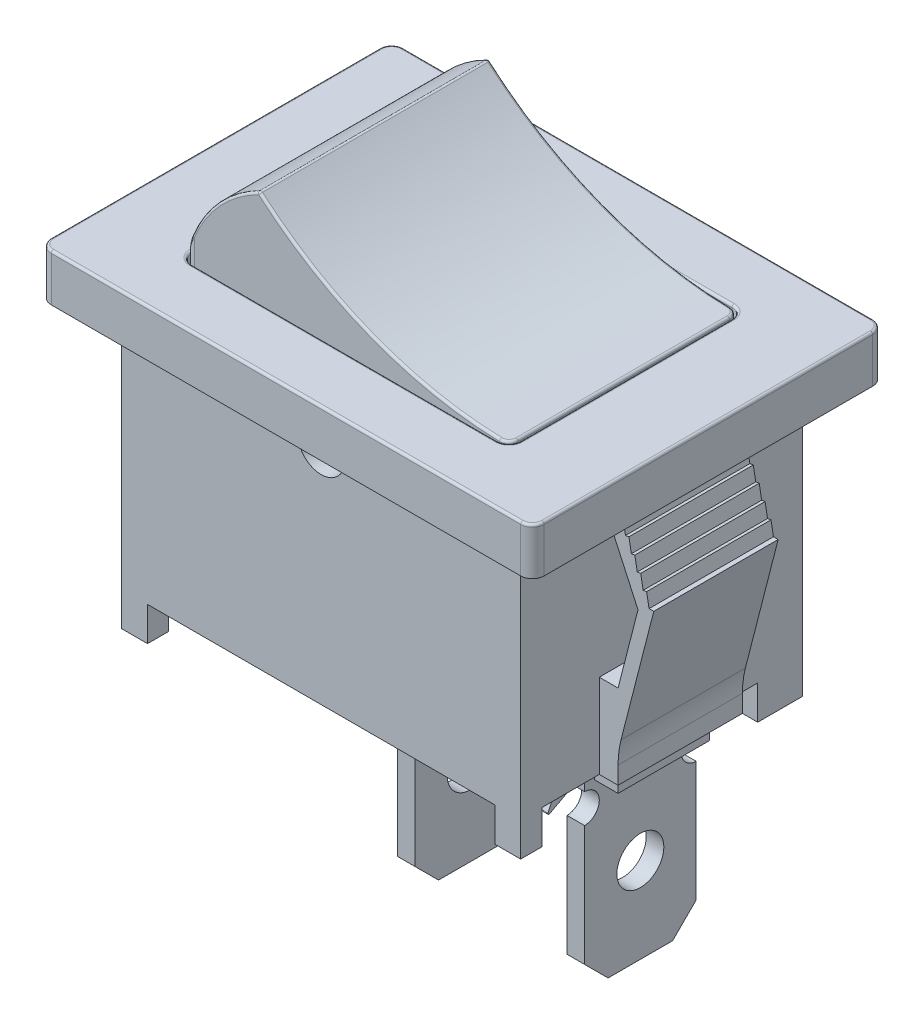
SolidWorks part; units mm, degrees
ref_plane "Front Plane" through (0, 0, 0) normal (0, 0, 1) x (1, 0, 0)
ref_plane "Top Plane" through (0, 0, 0) normal (0, 1, 0) x (1, 0, 0)
ref_plane "Right Plane" through (0, 0, 0) normal (1, 0, 0) x (0, 0, -1)
sketch "Sketch1" plane through (0, 0, 0) normal (0, 1, 0) x (1, 0, 0)
  line L0 (-8.5, 6) -> (8.5, -6) construction
  line L1 (-8.5, 6) -> (8.5, 6)
  line L2 (-8.5, 6) -> (-8.5, -6)
  line L3 (-8.5, -6) -> (8.5, -6)
  line L4 (8.5, 6) -> (8.5, -6)
  point P4 (0, 0)
  dimension "D1" = 17
  dimension "D2" = 12
extrude "Boss-Extrude1" add sketch "Sketch1" along normal blind 10.5
sketch "Sketch2" plane through (0, 10.5, 0) normal (0, 1, 0) x (1, 0, 0)
  line L0 (-10.5, 7.5) -> (10.5, -7.5) construction
  line L1 (-10.5, 7.5) -> (10.5, 7.5)
  line L2 (-10.5, 7.5) -> (-10.5, -7.5)
  line L3 (-10.5, -7.5) -> (10.5, -7.5)
  line L4 (10.5, 7.5) -> (10.5, -7.5)
  line L5 (7, 5) -> (-7, -5) construction
  line L6 (-6.5, 5) -> (6.5, 5)
  line L7 (-7, 4.5) -> (-7, -4.5)
  line L8 (-6.5, -5) -> (6.5, -5)
  line L9 (7, 4.5) -> (7, -4.5)
  arc A0 (6.5, 5) -> (7, 4.5) centre (6.5, 4.5) cw
  arc A1 (6.5, -5) -> (7, -4.5) centre (6.5, -4.5) ccw
  arc A2 (-7, -4.5) -> (-6.5, -5) centre (-6.5, -4.5) ccw
  arc A3 (-6.5, 5) -> (-7, 4.5) centre (-6.5, 4.5) ccw
  point P4 (0, 0)
  point P15 (7, -5)
  point P21 (-7, 5)
  dimension "D4" = 0.5
  dimension "D1" = 15
  dimension "D2" = 21
  dimension "D3" = 10
extrude "Boss-Extrude2" add sketch "Sketch2" along normal blind 2
sketch "Sketch3" plane through (0, 10.5, 0) normal (0, 1, 0) x (1, 0, 0)
  line L0 (7, -4.5) -> (7, 4.5) construction
  line L1 (-6.5, 5) -> (6.5, 5) construction
  line L2 (-7, 4.5) -> (-7, -4.5) construction
  line L3 (-6.5, -5) -> (6.5, -5) construction
  line L4 (7, 4.5) -> (7, -4.5) construction
  line L5 (-7, 4.5) -> (-7, -4.5) construction
  line L6 (-6.5, -5) -> (6.5, -5) construction
  line L7 (6.5, 5) -> (-6.5, 5) construction
  line L8 (-6.5, 4.9) -> (6.5, 4.9)
  line L9 (6.9, 4.5) -> (6.9, -4.5)
  line L10 (-6.5, -4.9) -> (6.5, -4.9)
  line L11 (-6.9, 4.5) -> (-6.9, -4.5)
  arc A0 (6.5, 5) -> (7, 4.5) centre (6.5, 4.5) cw construction
  arc A1 (-7, -4.5) -> (-6.5, -5) centre (-6.5, -4.5) ccw construction
  arc A2 (6.5, -5) -> (7, -4.5) centre (6.5, -4.5) ccw construction
  arc A3 (-6.5, 5) -> (-7, 4.5) centre (-6.5, 4.5) ccw construction
  arc A4 (6.5, 4.9) -> (6.9, 4.5) centre (6.5, 4.5) cw
  arc A5 (6.5, -4.9) -> (6.9, -4.5) centre (6.5, -4.5) ccw
  arc A6 (-6.9, -4.5) -> (-6.5, -4.9) centre (-6.5, -4.5) ccw
  arc A7 (-6.5, 4.9) -> (-6.9, 4.5) centre (-6.5, 4.5) ccw
  dimension "D1" = 0.5
  dimension "D2" = 0.1
extrude "Boss-Extrude3" add sketch "Sketch3" along normal blind 6
sketch "Sketch4" plane through (0, 0, 4.9) normal (0, 0, 1) x (1, 0, 0)
  line L2 (-6.5, 16.5) -> (6.5, 16.5) construction
  line L3 (-10.5, 12.5) -> (10.5, 12.5) construction
  line L4 (-10.5, 12.5) -> (-10.5, 10.5) construction
  line L6 (-6.9, 12.5) -> (6.9, 12.5) construction
  line L7 (-6.9, 12.5) -> (-6.9, 16.5)
  line L8 (-6.9, 16.5) -> (6.9, 16.5)
  line L9 (6.9, 16.5) -> (6.9, 12.5)
  line L10 (6.9, 16.5) -> (6.9, 10.5) construction
  arc A0 (-3.75, 16.5) -> (6.9, 12.5) centre (6.9, 28.6778) ccw
  arc A1 (-3.75, 16.5) -> (-6.9, 12.5) centre (-1.2, 11.2516) ccw
  point P2 (-3.75, 16.5)
  point P4 (6.5, 12.5)
  point P6 (-6.9, 12.5)
  point P7 (4.5, 12.5)
  dimension "D2" = 6.75
extrude "Cut-Extrude1" cut sketch "Sketch4" against normal blind 11
fillet "Fillet1" radius 0.1 23 edges at (1.025, 13.6045, -4.9) (-5.3685, 15.3348, -4.9) (-6.8601, 12.67, -4.6742) (-6.9, 12.5, 0) (-6.8943, 12.5256, 4.5672) (-3.75, 16.5, 0) (1.025, 13.6045, 4.9) (-5.3685, 15.3348, 4.9) (0, 12.5, -7.5) (10.5, 12.5, 0) (0, 12.5, 7.5) (-10.5, 12.5, 0) (-6.8536, 12.5, -4.8536) (-7, 12.5, 0) (-6.8536, 12.5, 4.8536) (0, 12.5, 5) (6.8536, 12.5, 4.8536) (7, 12.5, 0) (6.8536, 12.5, -4.8536) (0, 12.5, -5) (6.7498, 12.5007, -4.8124) (6.9, 12.5, 0) (6.8123, 12.5002, 4.7499)
fillet "Fillet2" radius 0.5 8 edges at (-10.4707, 12.4707, 7.4707) (10.4707, 12.4707, 7.4707) (10.4707, 12.4707, -7.4707) (-10.4707, 12.4707, -7.4707) (-10.5, 11.45, -7.5) (10.5, 11.45, -7.5) (10.5, 11.45, 7.5) (-10.5, 11.45, 7.5)
sketch "Sketch5" plane through (0, 0, 0) normal (0, 0, 1) x (1, 0, 0)
  line L0 (8.5, 10.5) -> (10.15, 6.9)
  line L1 (10.15, 6.9) -> (9.3, 3.5879)
  line L2 (9.3, 3.5879) -> (8.5, 3.5879)
  line L3 (8.5, 10.5) -> (8.5, 0) construction
  line L4 (9.1, 10.5) -> (10.6218, 7.1797) construction
  line L5 (-10, 10.5) -> (10, 10.5) construction
  line L6 (10.8218, 7.1797) -> (9.4256, 1.7392)
  line L7 (9.3, 0.7449) -> (9.3, 0)
  line L8 (9.3, 0) -> (8.5, 0)
  line L9 (8.5, 0) -> (8.5, 3.5879)
  line L10 (10.15, 6.9) -> (10.75, 6.9) construction
  line L11 (9.3, 3.5879) -> (9.3, 1.25) construction
  line L12 (8.5, 10.5) -> (9.1, 10.5)
  line L13 (10.6218, 7.1797) -> (10.8218, 7.1797)
  line L14 (10.6218, 7.1797) -> (10.5178, 7.7553)
  line L15 (10.5178, 7.7553) -> (10.3702, 7.7287)
  line L16 (10.3702, 7.7287) -> (10.2662, 8.3043)
  line L17 (10.2662, 8.3043) -> (10.1186, 8.2776)
  line L18 (10.1186, 8.2776) -> (10.0146, 8.8532)
  line L19 (10.0146, 8.8532) -> (9.867, 8.8265)
  line L20 (9.867, 8.8265) -> (9.763, 9.4021)
  line L21 (9.763, 9.4021) -> (9.6154, 9.3755)
  line L22 (9.6154, 9.3755) -> (9.5114, 9.9511)
  line L23 (9.5114, 9.9511) -> (9.3638, 9.9244)
  line L24 (9.3638, 9.9244) -> (9.2598, 10.5)
  line L25 (9.2598, 10.5) -> (9.1, 10.5)
  line L26 (0, 0) -> (0, -6.2218) construction
  line L27 (-9.3, 3.5879) -> (-9.3, 1.25) construction
  line L28 (-10.15, 6.9) -> (-10.75, 6.9) construction
  line L29 (-9.1, 10.5) -> (-10.6218, 7.1797) construction
  line L30 (-9.2598, 10.5) -> (-9.1, 10.5)
  line L31 (-9.3638, 9.9244) -> (-9.2598, 10.5)
  line L32 (-9.5114, 9.9511) -> (-9.3638, 9.9244)
  line L33 (-9.6154, 9.3755) -> (-9.5114, 9.9511)
  line L34 (-9.763, 9.4021) -> (-9.6154, 9.3755)
  line L35 (-9.867, 8.8265) -> (-9.763, 9.4021)
  line L36 (-10.0146, 8.8532) -> (-9.867, 8.8265)
  line L37 (-10.1186, 8.2776) -> (-10.0146, 8.8532)
  line L38 (-10.2662, 8.3043) -> (-10.1186, 8.2776)
  line L39 (-10.3702, 7.7287) -> (-10.2662, 8.3043)
  line L40 (-10.5178, 7.7553) -> (-10.3702, 7.7287)
  line L41 (-10.6218, 7.1797) -> (-10.5178, 7.7553)
  line L42 (-10.6218, 7.1797) -> (-10.8218, 7.1797)
  line L43 (-8.5, 10.5) -> (-9.1, 10.5)
  line L44 (-8.5, 0) -> (-8.5, 3.5879)
  line L45 (-9.3, 0) -> (-8.5, 0)
  line L46 (-9.3, 0.7449) -> (-9.3, 0)
  line L47 (-10.8218, 7.1797) -> (-9.4256, 1.7392)
  line L48 (-9.3, 3.5879) -> (-8.5, 3.5879)
  line L49 (-10.15, 6.9) -> (-9.3, 3.5879)
  line L50 (-8.5, 10.5) -> (-10.15, 6.9)
  arc A0 (-9.4256, 1.7392) -> (-9.3, 0.7449) centre (-13.3, 0.7449) cw
  arc A1 (9.4256, 1.7392) -> (9.3, 0.7449) centre (13.3, 0.7449) ccw
  dimension "D8" = 4
  dimension "D1" = 0.6
  dimension "D2" = 1.25
  dimension "D3" = 0.8
  dimension "D4" = 2.25
  dimension "D5" = 3.6
  dimension "D6" = 0.2
  dimension "D7" = 0.15
extrude "Boss-Extrude4" add sketch "Sketch5" along normal blind 2.65 and the other way blind 2.65
sketch "Sketch6" plane through (0, 0, 0) normal (0, -1, 0) x (1, 0, 0)
  line L0 (0, 0) -> (-16.4679, 0) construction
  line L1 (-8.6, 1.95) -> (-7.6, 1.95)
  line L2 (-8.6, 1.95) -> (-8.6, -1.95)
  line L3 (-8.6, -1.95) -> (-7.6, -1.95)
  line L4 (-7.6, 1.95) -> (-7.6, -1.95)
  line L5 (-9.3, -2.65) -> (-9.3, 2.65) construction
  line L6 (0, 8.4568) -> (0, 0) construction
  line L7 (0.375, 1.95) -> (0.375, -1.95)
  line L8 (-6.85, 1.95) -> (-5.85, 1.95)
  line L9 (-6.85, 1.95) -> (-6.85, -1.95)
  line L10 (-6.85, -1.95) -> (-5.85, -1.95)
  line L11 (-5.85, 1.95) -> (-5.85, -1.95)
  line L12 (-1.375, 1.95) -> (-0.375, 1.95)
  line L13 (-1.375, 1.95) -> (-1.375, -1.95)
  line L14 (-1.375, -1.95) -> (-0.375, -1.95)
  line L15 (-0.375, 1.95) -> (-0.375, -1.95)
  line L16 (1.375, -1.95) -> (0.375, -1.95)
  line L17 (1.375, 1.95) -> (1.375, -1.95)
  line L18 (1.375, 1.95) -> (0.375, 1.95)
  line L19 (5.85, 1.95) -> (5.85, -1.95)
  line L20 (6.85, -1.95) -> (5.85, -1.95)
  line L21 (6.85, 1.95) -> (6.85, -1.95)
  line L22 (6.85, 1.95) -> (5.85, 1.95)
  line L23 (7.6, 1.95) -> (7.6, -1.95)
  line L24 (8.6, -1.95) -> (7.6, -1.95)
  line L25 (8.6, 1.95) -> (8.6, -1.95)
  line L26 (8.6, 1.95) -> (7.6, 1.95)
  point P4 (-8.6, 0)
  dimension "D1" = 3.9
  dimension "D2" = 1
  dimension "D3" = 0.7
  dimension "D4" = 0.75
  dimension "D5" = 0.375
extrude "Boss-Extrude5" add sketch "Sketch6" along normal blind 1
sketch "Sketch7" plane through (0, 0, 0) normal (0, -1, 0) x (1, 0, 0)
  line L0 (0.375, 1.95) -> (0.375, -1.95) construction
  line L1 (-0.375, 4) -> (0.375, 4)
  line L2 (-0.375, 4) -> (-0.375, -4)
  line L3 (-0.375, -4) -> (0.375, -4)
  line L4 (0.375, 4) -> (0.375, -4)
  line L5 (6.85, 4) -> (7.6, 4)
  line L6 (6.85, 4) -> (6.85, -4)
  line L7 (6.85, -4) -> (7.6, -4)
  line L8 (7.6, 4) -> (7.6, -4)
  line L9 (6.85, -1.95) -> (6.85, 1.95) construction
  line L10 (0, 0) -> (14.1504, 0) construction
  point P13 (0.375, 0)
  dimension "D1" = 0.75
  dimension "D2" = 8
extrude "Boss-Extrude6" add sketch "Sketch7" along normal blind 8.6
sketch "Sketch8" plane through (7.6, 0, 0) normal (1, 0, 0) x (0, 0, -1)
  line L0 (4, -8.6) -> (-4, -8.6) construction
  line L1 (1.95, 0) -> (-1.95, 0) construction
  line L2 (-2.375, -0.5) -> (-2.375, -1.225)
  line L3 (4, -8.6) -> (1.375, -8.6)
  line L4 (4, 0) -> (4, -8.6)
  line L6 (-2.375, -7.6) -> (-1.375, -8.6)
  line L7 (3.375, 0) -> (4, 0)
  line L8 (0, -4.95) -> (0, 0) construction
  line L9 (-1.75, -1.85) -> (1.75, -1.85) construction
  line L10 (3.9384, -1.2292) -> (3.375, 0)
  line L11 (2.375, -0.5) -> (3.8695, -1.2942)
  line L12 (-2.375, -2.475) -> (-2.375, -7.6)
  line L13 (2.375, -2.475) -> (2.375, -7.6)
  line L14 (-2.375, -0.5) -> (-3.8695, -1.2942)
  line L15 (-4, -8.6) -> (-4, 0) construction
  line L16 (-3.9384, -1.2292) -> (-3.375, 0)
  line L17 (-1.95, 0) -> (-4, 0) construction
  line L18 (-6, 0) -> (-2.65, 0) construction
  line L19 (2.375, -7.6) -> (1.375, -8.6)
  line L20 (2.375, -0.5) -> (2.375, -1.225)
  line L21 (-3.375, 0) -> (-4, 0)
  line L22 (-4, 0) -> (-4, -8.6)
  line L23 (-4, -8.6) -> (-1.375, -8.6)
  circle A0 centre (0, -4.95) radius 1
  arc A1 (-2.375, -2.475) -> (-2.375, -1.225) centre (-2.375, -1.85) ccw
  arc A2 (3.8695, -1.2942) -> (3.9384, -1.2292) centre (3.893, -1.25) ccw
  arc A3 (-3.8695, -1.2942) -> (-3.9384, -1.2292) centre (-3.893, -1.25) cw
  arc A4 (2.375, -2.475) -> (2.375, -1.225) centre (2.375, -1.85) cw
  point P0 (0, 0)
  point P1 (2.375, -8.6)
  point P2 (-2.375, -8.6)
  point P6 (0, -8.6)
  point P7 (0, 0)
  point P13 (0, 0)
  point P17 (0, 0)
  point P18 (0, -1.85)
  point P39 (-4, -1.3635)
  point P45 (4, -1.3635)
  dimension "D2" = 2
  dimension "D10" = 0.05
  dimension "D5" = 0.625
  dimension "D1" = 4.75
  dimension "D3" = 1.75
  dimension "D6" = 5.125
  dimension "D7" = 0.725
  dimension "D8" = 0.5
  dimension "D9" = 1
  dimension "D11" = 1.25
  dimension "D12" = 2.375
  dimension "D13" = 3.65
  dimension "D14" = 1.85
  dimension "D15" = 37.389
extrude "Cut-Extrude2" cut sketch "Sketch8" against normal blind 8.6
sketch "Sketch9" plane through (0, 0, 0) normal (0, -1, 0) x (1, 0, 0)
  line L1 (-8.5, 6) -> (-7.4, 6)
  line L2 (-8.5, 6) -> (-8.5, 5.1)
  line L3 (-8.5, 5.1) -> (-7.4, 5.1)
  line L4 (-7.4, 6) -> (-7.4, 5.1)
  line L5 (8.5, 6) -> (7.4, 6)
  line L6 (8.5, 6) -> (8.5, 5.1)
  line L7 (8.5, 5.1) -> (7.4, 5.1)
  line L8 (7.4, 6) -> (7.4, 5.1)
  line L9 (-8.5, -6) -> (-6.6, -6)
  line L10 (-8.5, -6) -> (-8.5, -4.1)
  line L11 (-8.5, -4.1) -> (-6.6, -4.1)
  line L12 (-6.6, -6) -> (-6.6, -4.1)
  line L13 (8.5, -6) -> (6.6, -6)
  line L14 (8.5, -6) -> (8.5, -4.1)
  line L15 (8.5, -4.1) -> (6.6, -4.1)
  line L16 (6.6, -6) -> (6.6, -4.1)
  point P20 (-4.8134, -4.6462)
  point P21 (-4.6351, -3.1978)
  point P22 (-6.6, -4.1)
  dimension "D1" = 1.1
  dimension "D2" = 0.9
  dimension "D3" = 1.9
extrude "Boss-Extrude7" add sketch "Sketch9" along normal blind 1.45
sketch "Sketch10" plane through (0, 0, 6) normal (0, 0, 1) x (1, 0, 0)
  line L0 (0, 0) -> (0, 9.49) construction
  line L1 (-7.4, 0) -> (7.4, 0) construction
  line L3 (-10, 10.5) -> (10, 10.5) construction
  circle A0 centre (0, 9.49) radius 1
  dimension "D1" = 2
  dimension "D2" = 1.01
extrude "Cut-Extrude7" cut sketch "Sketch10" against normal blind 1
sketch "Sketch11" plane through (0, 0, -6) normal (0, 0, -1) x (-1, 0, 0)
  circle A0 centre (0, 9.49) radius 1
extrude "Cut-Extrude8" cut sketch "Sketch11" against normal blind 1
